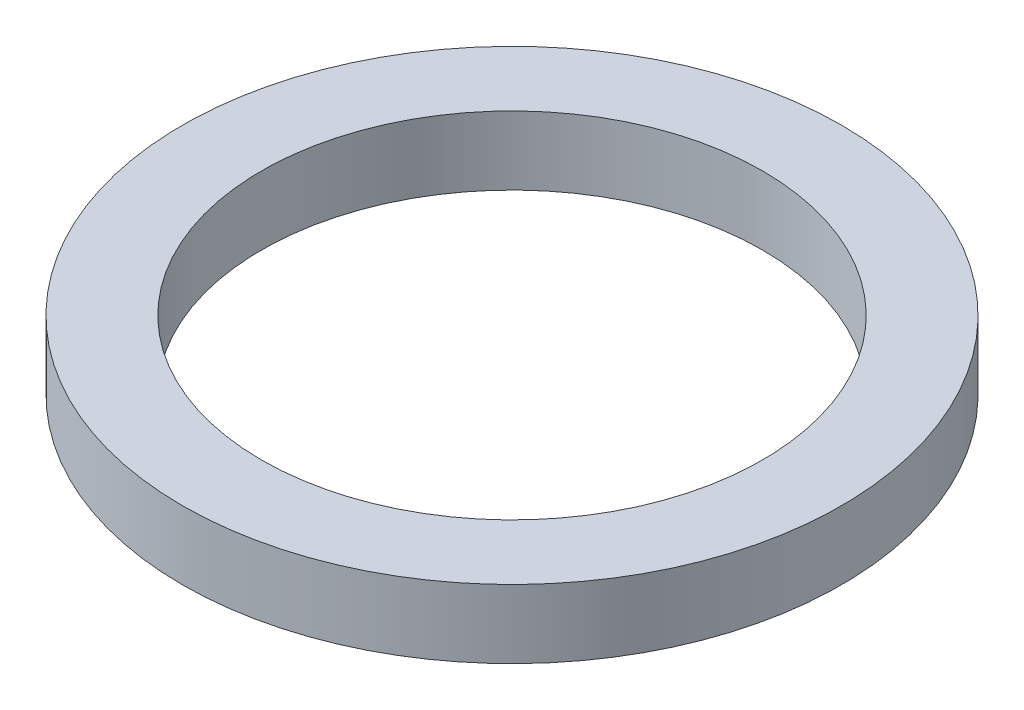
SolidWorks part; units mm, degrees
ref_plane "Front Plane" through (0, 0, 0) normal (0, 0, 1) x (1, 0, 0)
ref_plane "Top Plane" through (0, 0, 0) normal (0, 1, 0) x (1, 0, 0)
ref_plane "Right Plane" through (0, 0, 0) normal (1, 0, 0) x (0, 0, -1)
sketch "Sketch1" plane through (0, 0, 0) normal (0, 1, 0) x (1, 0, 0)
  circle A0 centre (0, 0) radius 62.5
  dimension "FLANGE_OD" = 125
extrude "Boss-Extrude1" add sketch "Sketch1" along normal blind 13
sketch "Sketch2" plane through (0, 0, 0) normal (0, 1, 0) x (1, 0, 0)
  circle A0 centre (0, 0) radius 47.5
  dimension "BORE_D" = 95
extrude "Cut-Extrude1" cut sketch "Sketch2" along normal through all
sketch "Sketch3" plane through (0, 13, 0) normal (0, 1, 0) x (1, 0, 0)
  circle A0 centre (0, 0) radius 26.8037 construction
  circle A1 centre (-26.8037, 0) radius 2.6385
  dimension "BOLT_D" = 5.2771
  dimension "BOLT_PCD" = 53.6074
extrude "Cut-Extrude2" cut sketch "Sketch3" against normal blind 8.2468 rebuild error yes
pattern_circular "CirPattern1" count 3 over 360 rebuild error yes
